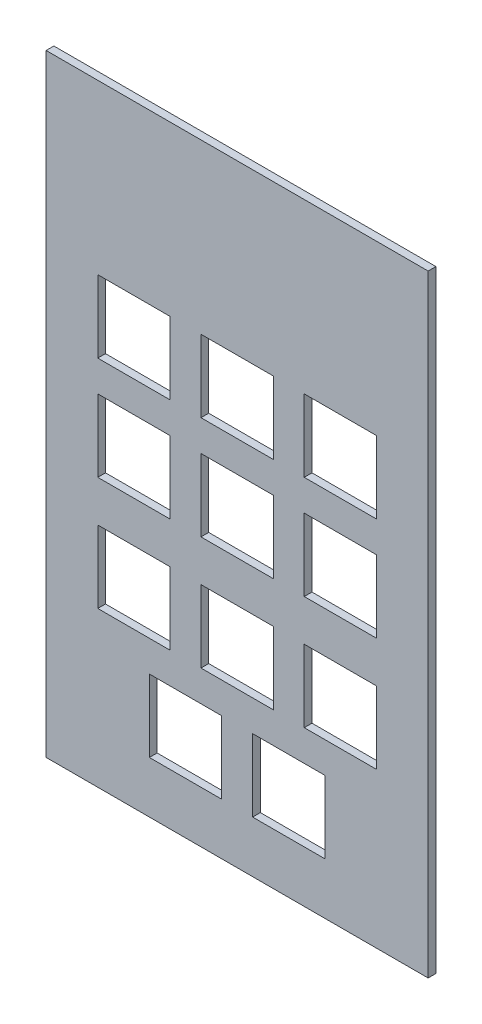
SolidWorks part; units mm, degrees
material "ABS"
ref_plane "Front Plane" through (0, 0, 0) normal (0, 0, 1) x (1, 0, 0)
ref_plane "Top Plane" through (0, 0, 0) normal (0, 1, 0) x (1, 0, 0)
ref_plane "Right Plane" through (0, 0, 0) normal (1, 0, 0) x (0, 0, -1)
sketch "Sketch1" plane through (0, 0, 0) normal (0, 0, 1) x (1, 0, 0)
  line L0 (-50, 30) -> (-44, 30) construction
  line L1 (0, 0) -> (-74, 0)
  line L2 (0, 0) -> (0, 118.61)
  line L3 (0, 118.61) -> (-74, 118.61)
  line L4 (-74, 0) -> (-74, 118.61)
  line L5 (-10, 44) -> (-24, 44)
  line L6 (-10, 72) -> (-24, 72)
  line L7 (-10, 72) -> (-10, 86)
  line L8 (-10, 86) -> (-24, 86)
  line L9 (-24, 72) -> (-24, 86)
  line L10 (-10, 44) -> (-10, 30)
  line L11 (-10, 30) -> (-24, 30)
  line L13 (-30, 86) -> (-44, 86)
  line L14 (-30, 86) -> (-30, 72)
  line L15 (-30, 72) -> (-44, 72)
  line L16 (-44, 86) -> (-44, 72)
  line L17 (-50, 86) -> (-64, 86)
  line L18 (-50, 86) -> (-50, 72)
  line L19 (-50, 72) -> (-64, 72)
  line L20 (-64, 86) -> (-64, 72)
  line L25 (-50, 72) -> (-44, 72) construction
  line L26 (-30, 72) -> (-24, 72) construction
  line L27 (-10, 52) -> (-24, 52)
  line L28 (-10, 52) -> (-10, 66)
  line L29 (-10, 66) -> (-24, 66)
  line L30 (-24, 52) -> (-24, 66)
  line L32 (-30, 66) -> (-44, 66)
  line L33 (-30, 66) -> (-30, 52)
  line L34 (-30, 52) -> (-44, 52)
  line L35 (-44, 66) -> (-44, 52)
  line L36 (-50, 66) -> (-64, 66)
  line L37 (-50, 66) -> (-50, 52)
  line L38 (-50, 52) -> (-64, 52)
  line L39 (-64, 66) -> (-64, 52)
  line L44 (-50, 52) -> (-44, 52) construction
  line L45 (-30, 52) -> (-24, 52) construction
  line L46 (-24, 44) -> (-24, 30)
  line L47 (-30, 44) -> (-44, 44)
  line L48 (-30, 44) -> (-30, 30)
  line L49 (-30, 30) -> (-44, 30)
  line L50 (-44, 44) -> (-44, 30)
  line L51 (-50, 44) -> (-64, 44)
  line L52 (-50, 44) -> (-50, 30)
  line L53 (-50, 30) -> (-64, 30)
  line L54 (-64, 44) -> (-64, 30)
  line L55 (-30, 30) -> (-24, 30) construction
  line L56 (-10, 72) -> (-10, 66) construction
  line L57 (-24, 52) -> (-24, 44) construction
  line L58 (-20, 24) -> (-34, 24)
  line L69 (-20, 24) -> (-20, 10)
  line L70 (-20, 10) -> (-34, 10)
  line L71 (-34, 24) -> (-34, 10)
  line L72 (-40, 24) -> (-54, 24)
  line L73 (-40, 24) -> (-40, 10)
  line L74 (-40, 10) -> (-54, 10)
  line L75 (-54, 24) -> (-54, 10)
  line L76 (-27, 30) -> (-27, 24) construction
  line L77 (-34, 17) -> (-40, 17) construction
  point P52 (0, 59.305)
  dimension "D3" = 14
  dimension "D4" = 6
  dimension "D5" = 14
  dimension "D7" = 8
  dimension "D2" = 10
  dimension "D1" = 10
  dimension "D10" = 10
  dimension "D6" = 32.61
extrude "Boss-Extrude1" add sketch "Sketch1" along normal blind 1.5
equation "\"D2@Sketch1\"=\"D10@Sketch1\""
equation "\"D1@Sketch1\"=\"D10@Sketch1\""
